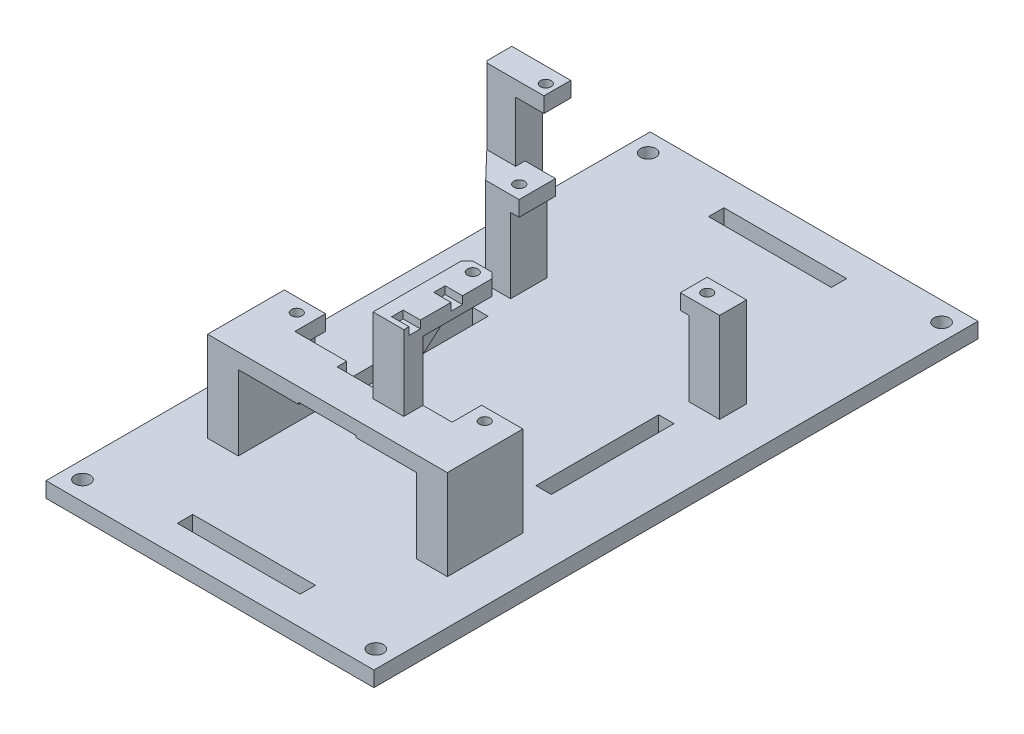
SolidWorks part; units mm, degrees
material "PLA_Base"
ref_plane "Front Plane" through (0, 0, 0) normal (0, 0, 1) x (1, 0, 0)
ref_plane "Top Plane" through (0, 0, 0) normal (0, 1, 0) x (1, 0, 0)
ref_plane "Right Plane" through (0, 0, 0) normal (1, 0, 0) x (0, 0, -1)
sketch "Sketch1" plane through (0, 0, 0) normal (0, 1, 0) x (1, 0, 0)
  line L1 (-42.75, 78.75) -> (42.75, 78.75)
  line L2 (-42.75, 78.75) -> (-42.75, -78.75)
  line L3 (-42.75, -78.75) -> (42.75, -78.75)
  line L4 (42.75, 78.75) -> (42.75, -78.75)
  line L5 (-42.75, 78.75) -> (42.75, -78.75) construction
  line L6 (-42.75, -78.75) -> (42.75, 78.75) construction
  point P0 (0, 0)
  dimension "D1" = 157.5
  dimension "D2" = 85.5
extrude "Boss-Extrude1" add sketch "Sketch1" along normal blind 4
sketch "Sketch2" plane through (0, 4, 0) normal (0, 1, 0) x (1, 0, 0)
  line L0 (-42.75, -78.75) -> (42.75, -78.75) construction
  line L1 (42.75, -78.75) -> (42.75, 78.75) construction
  line L2 (0, 0) -> (50000, 0) construction
  line L3 (0, 0) -> (0, -50000) construction
  circle A0 centre (38.25, -73.75) radius 2
  circle A1 centre (38.25, 73.75) radius 2
  circle A2 centre (-38.25, -73.75) radius 2
  circle A3 centre (-38.25, 73.75) radius 2
  dimension "D1" = 4
  dimension "D2" = 5
  dimension "D3" = 4.5
extrude "Cut-Extrude1" cut sketch "Sketch2" against normal up to next
sketch "Sketch5" plane through (0, 4, 0) normal (0, 1, 0) x (1, 0, 0)
  line L0 (-24.5, 26.3886) -> (-24.5, -31.6114) construction
  line L1 (-24.5, -31.6114) -> (24.5, -31.6114) construction
  line L2 (24.5, -31.6114) -> (24.5, 26.3886) construction
  line L3 (24.5, 26.3886) -> (-24.5, 26.3886) construction
  line L4 (0, 49.8886) -> (0, -35.1114) construction
  line L5 (-22.25, 67.25) -> (22.25, 67.25) construction
  line L6 (-22.25, 67.25) -> (-22.25, -67.25) construction
  line L7 (-22.25, -67.25) -> (22.25, -67.25) construction
  line L8 (22.25, 67.25) -> (22.25, -67.25) construction
  line L9 (-22.25, 67.25) -> (22.25, -67.25) construction
  line L10 (-22.25, -67.25) -> (22.25, 67.25) construction
  line L11 (-28, 49.8886) -> (28, 49.8886) construction
  line L12 (-28, 49.8886) -> (-28, -35.1114) construction
  line L13 (-28, -35.1114) -> (28, -35.1114) construction
  line L14 (28, 49.8886) -> (28, -35.1114) construction
  line L15 (24.5, 26.3886) -> (23.25, 26.3886) construction
  line L16 (-37, 36.9499) -> (-29, 36.9499)
  line L18 (-29.75, 22.8886) -> (-23.25, 22.8886)
  line L19 (-23.25, 32.3886) -> (-23.25, 22.8886)
  line L20 (23.25, 29.8886) -> (31.25, 29.8886)
  line L21 (23.25, 29.8886) -> (23.25, 22.8886)
  line L22 (23.25, 22.8886) -> (31.25, 22.8886)
  line L23 (31.25, 29.8886) -> (31.25, 22.8886)
  line L24 (-23.25, -48.1114) -> (23.25, -48.1114) construction
  line L25 (-31.25, -28.1114) -> (-23.25, -28.1114)
  line L26 (-31.25, -28.1114) -> (-31.25, -48.1114)
  line L27 (-31.25, -48.1114) -> (-23.25, -48.1114)
  line L28 (-23.25, -28.1114) -> (-23.25, -48.1114)
  line L29 (23.25, -28.4114) -> (31.25, -28.4114)
  line L30 (23.25, -28.4114) -> (23.25, -48.1114)
  line L31 (23.25, -48.1114) -> (31.25, -48.1114)
  line L32 (31.25, -28.4114) -> (31.25, -48.1114)
  line L33 (22.25, -16) -> (26.25, -16)
  line L34 (-22.25, -16) -> (-26.25, -16)
  line L35 (-22.25, -16) -> (-22.25, 16)
  line L36 (-22.25, 16) -> (-26.25, 16)
  line L37 (-26.25, -16) -> (-26.25, 16)
  line L38 (22.25, -16) -> (22.25, 16)
  line L39 (26.25, -16) -> (26.25, 16)
  line L40 (22.25, 16) -> (26.25, 16)
  line L41 (-23.25, 32.3886) -> (-29, 32.3886)
  line L42 (-29, 32.3886) -> (-29, 36.9499)
  line L43 (-37, 36.9499) -> (-37, 30.4499)
  line L44 (-37, 30.4499) -> (-29.75, 22.8886)
  line L46 (-42.75, 0) -> (42.75, 0) construction
  line L47 (-16, 67.25) -> (16, 67.25)
  line L48 (-16, 67.25) -> (-16, 71.25)
  line L49 (-16, 71.25) -> (16, 71.25)
  line L50 (16, 67.25) -> (16, 71.25)
  line L51 (-42.75, 78.75) -> (-42.75, -78.75) construction
  line L52 (42.75, -78.75) -> (42.75, 78.75) construction
  line L53 (16, -67.25) -> (16, -71.25)
  line L54 (-16, -71.25) -> (16, -71.25)
  line L55 (-16, -67.25) -> (-16, -71.25)
  line L56 (-16, -67.25) -> (16, -67.25)
  circle A0 centre (-24.5, 26.3886) radius 1.4
  circle A1 centre (-24.13, 32.9499) radius 1.4
  circle A2 centre (8.89, -19.1201) radius 1.4
  circle A3 centre (24.5, -31.6114) radius 1.4
  circle A4 centre (24.5, 26.3886) radius 1.4
  circle A5 centre (-24.5, -31.6114) radius 1.4
  point P9 (0, 0)
  point P32 (23.25, 26.3886)
  point P46 (-22.25, 0)
  point P58 (0, 67.25)
  point P69 (0, -67.25)
  dimension "D1" = 24.5
  dimension "D2" = 26.3886
  dimension "D3" = 32.9499
  dimension "D4" = 24.13
  dimension "D5" = 2.8
  dimension "D6" = 33.02
  dimension "D7" = 52.07
  dimension "D8" = 49
  dimension "D9" = 58
  dimension "D18" = 4
  dimension "D21" = 3.5
  dimension "D24" = 3.5
  dimension "D10" = 44.5
  dimension "D11" = 134.5
  dimension "D12" = 56
  dimension "D13" = 85
  dimension "D14" = 28
  dimension "D15" = 3.5
  dimension "D16" = 1
  dimension "D17" = 3.5
  dimension "D19" = 6.5
  dimension "D20" = 1
  dimension "D22" = 8
  dimension "D23" = 1
  dimension "D25" = 1
  dimension "D26" = 3.2
  dimension "D27" = 8
  dimension "D28" = 8
  dimension "D29" = 20
  dimension "D30" = 32
  dimension "D31" = 4
  dimension "D32" = 6
  dimension "D33" = 1
  dimension "D34" = 8
  dimension "D35" = 6.5
  dimension "D36" = 32
  dimension "D37" = 4
extrude "Cut-Extrude3" cut sketch "Sketch5" against normal up to next contours L37 L34 L35 L36 | L47 L50 L49 L48 | L56 L55 L54 L53 | L39 L40 L38 L33 region at (-24.25, 4, 0) region at (0, 4, -69.25) region at (0, 4, 69.25)
extrude "Boss-Extrude3" add sketch "Sketch5<3>" along normal blind 23.5 contours L32 L29 L30 L31 | L28 L25 L26 L27 | L23 L20 L21 L22 | L43 L44 L18 L19 L41 L42 L16 | L28 A5 | L30 A3 | L21 A4 | L19 A0 | L41 A1 L19 region at (-30.3132, 4, -30.0503) region at (-24.2191, 4, -32.0291) region at (-24.5277, 4, -26.3886) region at (27.5785, 4, -26.3886) region at (24.5277, 4, -26.3886) region at (-27.3566, 4, 38.366) region at (-24.5277, 4, 31.6114) region at (27.3583, 4, 38.526) region at (24.5277, 4, 31.6114)
sketch "Sketch5<3>" plane through (0, 4, 0) normal (0, 1, 0) x (1, 0, 0) same geometry as "Sketch5"
sketch "Sketch6" plane through (-23.25, 0, 0) normal (1, 0, 0) x (0, 0, -1)
  line L0 (-28.1114, 27.5) -> (-28.1114, 4) construction
  line L1 (-48.1114, 27.5) -> (-28.1114, 27.5)
  line L2 (-48.1114, 27.5) -> (-48.1114, 23.5)
  line L3 (-48.1114, 23.5) -> (-28.1114, 23.5)
  line L4 (-28.1114, 27.5) -> (-28.1114, 23.5)
  dimension "D1" = 4
extrude "Boss-Extrude5" add sketch "Sketch6" along normal up to surface (46.5 mm away) up to face at (23.25, 15.75, 38.2614)
sketch "Sketch7" plane through (0, 27.5, 0) normal (0, 1, 0) x (1, 0, 0)
  line L0 (-31.25, -28.1114) -> (23.25, -28.1114) construction
  line L1 (-20.5, -28.1114) -> (23.25, -28.1114)
  line L2 (-20.5, -28.1114) -> (-20.5, -36.1114)
  line L3 (-20.5, -36.1114) -> (20.5, -36.1114)
  line L4 (20.5, -28.4114) -> (20.5, -36.1114)
  line L5 (23.25, -28.4114) -> (20.5, -28.4114)
  line L6 (23.25, -28.1114) -> (23.25, -28.4114)
  line L7 (-31.25, -28.1114) -> (-31.25, -48.1114) construction
  line L8 (31.25, -28.4114) -> (31.25, -48.1114) construction
  dimension "D1" = 10.75
  dimension "D2" = 10.75
  dimension "D3" = 8
extrude "Cut-Extrude4" cut sketch "Sketch7" against normal up to next
sketch "Sketch8" plane through (23.25, 0, 0) normal (-1, 0, 0) x (0, 0, 1)
  line L0 (-22.8886, 27.5) -> (-22.8886, 4) construction
  line L1 (-29.8886, 27.5) -> (-22.8886, 27.5)
  line L2 (-29.8886, 27.5) -> (-29.8886, 23.5)
  line L3 (-29.8886, 23.5) -> (-22.8886, 23.5)
  line L4 (-22.8886, 27.5) -> (-22.8886, 23.5)
  dimension "D1" = 4
extrude "Boss-Extrude6" add sketch "Sketch8" along normal blind 2.25
sketch "Sketch9" plane through (-23.25, 0, 0) normal (1, 0, 0) x (0, 0, -1)
  line L0 (32.3886, 27.5) -> (32.3886, 4) construction
  line L1 (22.8886, 27.5) -> (32.3886, 27.5)
  line L2 (22.8886, 27.5) -> (22.8886, 23.5)
  line L3 (22.8886, 23.5) -> (32.3886, 23.5)
  line L4 (32.3886, 27.5) -> (32.3886, 23.5)
  dimension "D1" = 4
extrude "Boss-Extrude7" add sketch "Sketch9" along normal blind 2.2
extrude "Cut-Extrude5" cut sketch "Sketch5<5>" against normal blind 3.5 from surface contours A0 | A4 | A3 | A5 starting at face at (0, 27.5, 35.1864)
sketch "Sketch5<5>" plane through (0, 4, 0) normal (0, 1, 0) x (1, 0, 0) same geometry as "Sketch5"
sketch "Sketch13" plane through (0, 27.5, 0) normal (0, 1, 0) x (1, 0, 0)
  line L0 (-29, 32.3886) -> (-29, 36.9499) construction
  line L1 (-37, 36.9499) -> (-29, 36.9499)
  line L2 (-37, 36.9499) -> (-37, 29.9499)
  line L3 (-37, 29.9499) -> (-29, 29.9499)
  line L4 (-29, 36.9499) -> (-29, 29.9499)
  line L5 (-20.5, -36.1114) -> (20.5, -36.1114) construction
  line L6 (4.89, -36.1114) -> (12.89, -36.1114)
  line L7 (4.89, -36.1114) -> (4.89, -41.1114)
  line L8 (4.89, -41.1114) -> (12.89, -41.1114)
  line L9 (12.89, -36.1114) -> (12.89, -41.1114)
  line L10 (8.89, -19.1201) -> (8.89, -36.1114) construction
  circle A0 centre (-24.13, 32.9499) radius 1.4 construction
  point P15 (8.89, -36.1114)
  dimension "D1" = 3
  dimension "D2" = 5
  dimension "D3" = 8
extrude "Boss-Extrude8" add sketch "Sketch13" along normal blind 19.6
sketch "Sketch23" plane through (0, 27.5, 0) normal (0, -1, 0) x (1, 0, 0)
  line L3 (-37, -29.9499) -> (-37, -30.4499)
  line L4 (-37, -30.4499) -> (-36.5206, -29.9499)
  line L5 (-36.5206, -29.9499) -> (-37, -29.9499)
  line L6 (-37, -29.9499) -> (-37, -30.4499)
  line L7 (-37, -30.4499) -> (-36.5206, -29.9499)
  line L8 (-36.5206, -29.9499) -> (-37, -29.9499)
  dimension "D1" = 0
extrude "Cut-Extrude11" cut sketch "Sketch23" against normal up to next
sketch "Sketch14" plane through (-29, 0, 0) normal (1, 0, 0) x (0, 0, -1)
  line L0 (36.9499, 47.1) -> (36.9499, 4) construction
  line L1 (29.9499, 47.1) -> (36.9499, 47.1)
  line L2 (29.9499, 47.1) -> (29.9499, 43.1)
  line L3 (29.9499, 43.1) -> (36.9499, 43.1)
  line L4 (36.9499, 47.1) -> (36.9499, 43.1)
  dimension "D1" = 4
extrude "Boss-Extrude9" add sketch "Sketch14" along normal blind 7.37
sketch "Sketch15" plane through (0, 0, 36.1114) normal (0, 0, -1) x (-1, 0, 0)
  line L0 (-4.89, 47.1) -> (-4.89, 27.5) construction
  line L1 (-12.89, 47.1) -> (-4.89, 47.1)
  line L2 (-12.89, 47.1) -> (-12.89, 43.1)
  line L3 (-12.89, 43.1) -> (-4.89, 43.1)
  line L4 (-4.89, 47.1) -> (-4.89, 43.1)
  dimension "D1" = 4
extrude "Boss-Extrude10" add sketch "Sketch15" along normal blind 19.4913
extrude "Cut-Extrude6" cut sketch "Sketch5<6>" against normal up to next from surface contours A2 | A1 starting at face at (-30.7561, 47.1, -32.8499)
sketch "Sketch5<6>" plane through (0, 4, 0) normal (0, 1, 0) x (1, 0, 0) same geometry as "Sketch5"
sketch "Sketch16" plane through (0, 47.1, 0) normal (0, 1, 0) x (1, 0, 0)
  line L0 (8.89, -19.1201) -> (8.89, -27.2991) construction
  line L1 (8.89, -27.2991) -> (12.89, -27.2991) construction
  line L2 (12.89, -41.1114) -> (12.89, -16.6201) construction
  line L3 (8.39, -28.7991) -> (12.89, -28.7991)
  line L4 (8.39, -25.7991) -> (8.39, -28.7991)
  line L5 (8.39, -25.7991) -> (12.89, -25.7991)
  line L6 (8.39, -39.7721) -> (12.89, -39.7721)
  line L7 (8.89, -28.2991) -> (12.89, -28.2991) construction
  line L8 (8.89, -26.2991) -> (12.89, -26.2991) construction
  line L10 (8.89, -26.2991) -> (8.89, -28.2991) construction
  line L11 (8.89, -27.2991) -> (8.89, -38.2721) construction
  line L12 (8.89, -38.2721) -> (12.89, -38.2721) construction
  line L13 (12.89, -41.1114) -> (12.89, -36.1114) construction
  line L14 (8.89, -39.2721) -> (12.89, -39.2721) construction
  line L15 (8.89, -37.2721) -> (12.89, -37.2721) construction
  line L16 (8.89, -37.2721) -> (8.89, -39.2721) construction
  line L18 (8.39, -36.7721) -> (8.39, -39.7721)
  line L19 (8.39, -36.7721) -> (12.89, -36.7721)
  line L20 (12.89, -25.7991) -> (12.89, -28.7991)
  line L21 (12.89, -36.7721) -> (12.89, -39.7721)
  dimension "D1" = 8.179
  dimension "D2" = 1
  dimension "D4" = 10.973
  dimension "D5" = 1
  dimension "D7" = 0.5
  dimension "D3" = 1
  dimension "D6" = 1
extrude "Cut-Extrude7" cut sketch "Sketch16" against normal blind 2
chamfer "Chamfer1" distance 1.5 angle 45 2 edges at (4.89, 45.1, 16.6201) (12.89, 45.1, 16.6201)
ref_plane "Plane1" through (8.89, 0, 0) normal (-1, 0, 0) x (0, 0, 1)
sketch "Sketch19" plane through (8.89, 0, 0) normal (-1, 0, 0) x (0, 0, 1)
  line L0 (27.1157, 43.1) -> (36.1114, 35.3)
  line L1 (18.1201, 43.1) -> (36.1114, 43.1) construction
  line L2 (36.1114, 43.1) -> (36.1114, 27.5) construction
  line L3 (27.1157, 43.1) -> (36.1114, 43.1)
  line L4 (36.1114, 43.1) -> (36.1114, 35.3)
extrude "Boss-Extrude11" add sketch "Sketch19" along normal blind 2 and the other way blind 2
sketch "Sketch20" plane through (0, 0, -36.9499) normal (0, 0, -1) x (-1, 0, 0)
  line L1 (37, 4) -> (31.25, 4)
  line L2 (37, 4) -> (37, 10)
  line L3 (37, 10) -> (31.25, 10)
  line L4 (31.25, 4) -> (31.25, 10)
  dimension "D1" = 5.75
  dimension "D2" = 6
extrude "Cut-Extrude8" cut sketch "Sketch20" against normal up to next
chamfer "Chamfer2" distance 5.75 angle 45 1 edges at (-37, 10, -33.6999)
sketch "Sketch21" plane through (0, 0, -36.9499) normal (0, 0, -1) x (-1, 0, 0)
  line L1 (31.25, 10) -> (29, 10)
  line L2 (31.25, 10) -> (31.25, 4)
  line L3 (31.25, 4) -> (29, 4)
  line L4 (29, 10) -> (29, 4)
extrude "Cut-Extrude9" cut sketch "Sketch21" against normal up to surface (4.5613 mm away) up to face at (-24.4333, 18.3333, -32.3886)
chamfer "Chamfer3" distance 5.75 distance2 4.5613 1 edges at (-30.125, 10, -36.9499) first distance on face at (-29.5014, 30.8786, -36.9499)
sketch "Sketch22" plane through (0, 27.5, 0) normal (0, 1, 0) x (1, 0, 0)
  line L0 (0, -48.1114) -> (0, -36.1114) construction
  line L1 (-31.25, -48.1114) -> (31.25, -48.1114) construction
  line L2 (-20.5, -36.1114) -> (4.89, -36.1114) construction
  line L3 (-7, -36.1114) -> (-7, -38.6114)
  line L4 (-7, -38.6114) -> (7, -38.6114)
  line L5 (7, -38.6114) -> (7, -36.1114)
  line L6 (7, -36.1114) -> (-7, -36.1114)
  point P13 (0, -36.1114)
  dimension "D1" = 14
  dimension "D2" = 2.5
extrude "Cut-Extrude10" cut sketch "Sketch22" against normal blind 2.5
chamfer "Chamfer4" distance 2.5 angle 45 1 edges at (5.945, 27.5, 36.1114)
sketch "Sketch24" plane through (0, 23.5, 0) normal (0, -1, 0) x (1, 0, 0)
  line L0 (0, 48.1114) -> (0, 36.1114) construction
  line L1 (23.25, 48.1114) -> (-23.25, 48.1114) construction
  line L2 (20.5, 36.1114) -> (-20.5, 36.1114) construction
  line L3 (-7.5, 48.1114) -> (-7.5, 36.1114)
  line L4 (7.5, 48.1114) -> (7.5, 36.1114)
  line L5 (-7.5, 48.1114) -> (7.5, 48.1114)
  line L6 (7.5, 36.1114) -> (-7.5, 36.1114)
  dimension "D1" = 7.5
  dimension "D2" = 7.5
extrude "Cut-Extrude12" cut sketch "Sketch24" against normal blind 0.5
